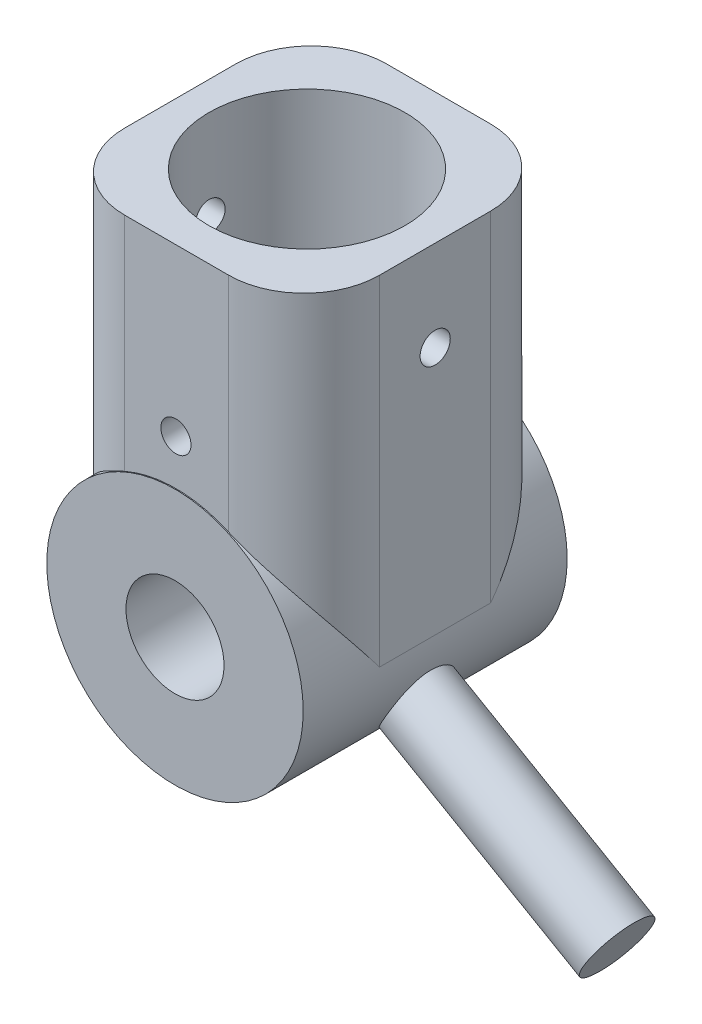
SolidWorks part; units mm, degrees
ref_plane "Спереди" through (0, 0, 0) normal (0, 0, 1) x (1, 0, 0)
ref_plane "Сверху" through (0, 0, 0) normal (0, 1, 0) x (1, 0, 0)
ref_plane "Справа" through (0, 0, 0) normal (1, 0, 0) x (0, 0, -1)
sketch "Эскиз1" plane through (0, 0, 0) normal (0, 0, 1) x (1, 0, 0)
  circle A0 centre (0, 0) radius 6.5
  circle A1 centre (0, 0) radius 17
extrude "Бобышка-Вытянуть2" add sketch "Эскиз1" along normal blind 35
ref_plane "Плоскость4" through (0, 45, 0) normal (0, 1, 0) x (1, 0, 0)
sketch "Эскиз3" plane through (0, 45, 0) normal (0, 1, 0) x (1, 0, 0)
  line L0 (17, -35) -> (17, 0) construction
  line L13 (-16.7953, -0.1471) -> (17, -0.1471)
  line L14 (-16.7953, -0.1471) -> (-16.7953, -34.8751)
  line L15 (-16.7953, -34.8751) -> (17, -34.8751)
  line L16 (17, -0.1471) -> (17, -34.8751)
  line L17 (-16.7953, -0.1471) -> (-17, 0) construction
  line L18 (-17, 0) -> (-17, -35) construction
  line L19 (-16.7953, -34.8751) -> (-17, -35) construction
  circle A1 centre (0, -17.5) radius 13
extrude "Бобышка-Вытянуть7" add sketch "Эскиз3" against normal blind 45
sketch "Эскиз4" plane through (0, 0, 0) normal (0, 0, -1) x (-1, 0, 0)
  circle A0 centre (0, 0) radius 6.5
extrude "Вырез-Вытянуть1" cut sketch "Эскиз4" against normal through all
sketch "Эскиз12" plane through (0, 0, 0) normal (0, 0, -1) x (-1, 0, 0)
  line L0 (0, 23) -> (0, 0) construction
  circle A3 centre (0, 23) radius 2
extrude "Вырез-Вытянуть11" cut sketch "Эскиз12" against normal blind 45
sketch "Эскиз15" plane through (-16.7953, 0, 0) normal (-1, 0, 0) x (0, 0, 1)
  line L0 (0, 0) -> (0, 33) construction
  line L1 (0, 33) -> (17.5, 33) construction
  circle A1 centre (17.5, 33) radius 2
extrude "Вырез-Вытянуть12" cut sketch "Эскиз15" against normal blind 45
fillet "Скругление4" radius 10 4 edges at (-16.7953, 23.8152, 0.1471) (17, 22.5, 0.1471) (17, 22.5, 34.8751) (-16.7953, 23.8152, 34.8751)
sketch "Эскиз20" plane through (0, 45, 0) normal (0, 1, 0) x (1, 0, 0)
  circle A3 centre (0, -17.5) radius 13
extrude "Вырез-Вытянуть18" cut sketch "Эскиз20" against normal blind 31
sketch "Эскиз25" plane through (0, 14, 0) normal (0, 1, 0) x (1, 0, 0)
  circle A2 centre (0, -17.5) radius 13
extrude "Бобышка-Вытянуть10" add sketch "Эскиз25" along normal blind 1
sketch3d "Трехмерный эскиз1"
  point P0 (-14.7779, 8.4033, 37.4657)
sketch "Эскиз26" plane through (0, 0, 0) normal (0, 0, -1) x (-1, 0, 0)
  circle A0 centre (0, 0) radius 11.25
extrude "Вырез-Вытянуть19" cut sketch "Эскиз26" against normal blind 7.5
sketch3d "Трехмерный эскиз4"
  point P0 (0.8909, -16.9766, 11.3566)
sketch3d "Трехмерный эскиз5"
  point P0 (15.2365, -7.5398, 9.0171)
sketch3d "Трехмерный эскиз6"
  point P0 (16.5585, -3.8494, 24.0123)
sketch3d "Трехмерный эскиз7"
  point P0 (15.9928, -5.7645, 14.4989)
sketch3d "Трехмерный эскиз8"
  point P0 (16.1648, -5.263, 16.1571)
sketch3d "Трехмерный эскиз9"
  point P0 (16.704, -3.1583, 20.9707)
ref_plane "Плоскость12" through (14.7224, -8.5, 0) normal (0.866, -0.5, 0) x (0, 0, -1)
sketch "Эскиз36" plane through (14.7224, -8.5, 0) normal (0.866, -0.5, 0) x (0, 0, -1)
  circle A0 centre (-17.5111, 0) radius 4.5
  circle A1 centre (-17.5111, 0) radius 2
extrude "Бобышка-Вытянуть17" add sketch "Эскиз36" along normal blind 15 and the other way up to body separate body
sketch "Эскиз40" plane through (27.7128, -16, 0) normal (0.866, -0.5, 0) x (0, 0, -1)
  line L0 (-15.9986, 2.6197) -> (-13.8523, 2.6197)
  line L2 (-15.9986, 2.6197) -> (-19.0236, 2.6197)
  line L3 (-19.0236, 2.6197) -> (-20.5361, 0)
  line L4 (-20.5361, 0) -> (-19.0236, -2.6197)
  line L5 (-19.0236, -2.6197) -> (-15.9986, -2.6197)
  line L7 (-14.4861, 0) -> (-15.9986, 2.6197)
  line L8 (-15.9986, -2.6197) -> (-14.4861, 0)
  line L9 (-15.9986, -2.6197) -> (-13.8523, -2.6197)
  arc A1 (-13.8523, 2.6197) -> (-13.8523, -2.6197) centre (-17.5111, 0) ccw
  arc A3 (-15.9986, 2.6197) -> (-15.9986, -2.6197) centre (-17.5111, 0) ccw construction
extrude "Бобышка-Вытянуть18" add sketch "Эскиз40" along normal blind 3.5
sketch "Эскиз41" plane through (30.7439, -17.75, 0) normal (0.866, -0.5, 0) x (0, 0, -1)
  circle A0 centre (-17.5111, 0) radius 4.5
extrude "Бобышка-Вытянуть19" add sketch "Эскиз41" along normal blind 12
sketch3d "Трехмерный эскиз10"
  point P0 (17, 16.7342, 15.5161)
